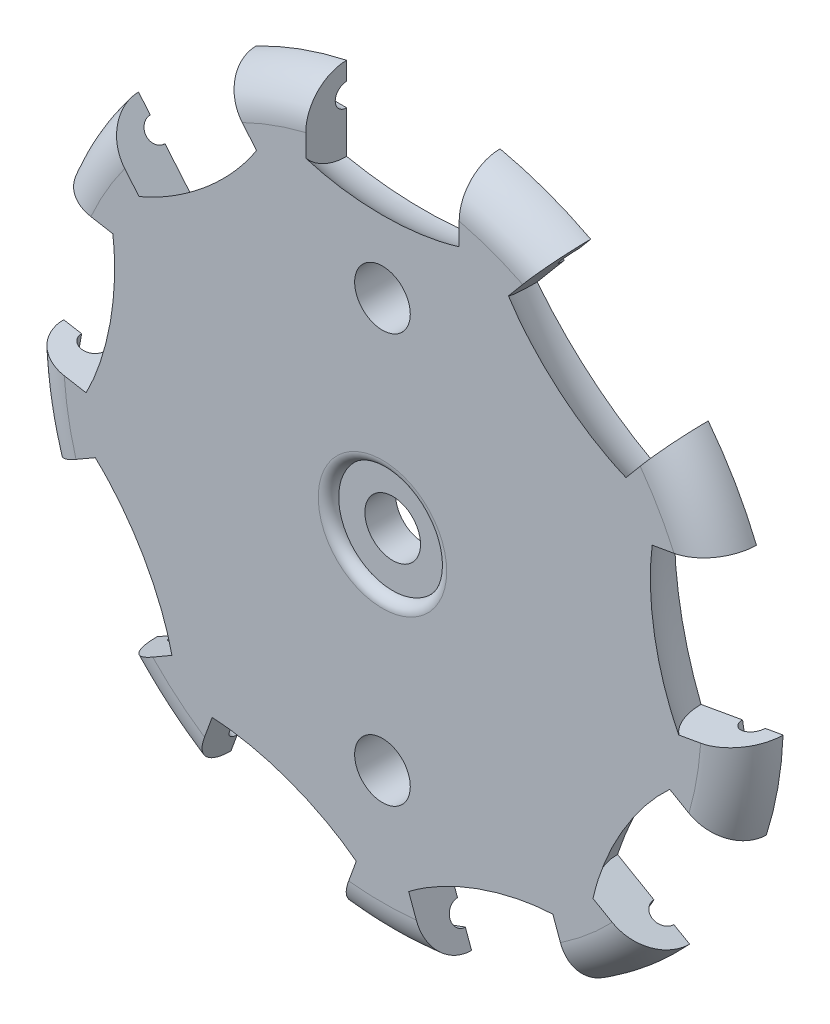
SolidWorks part; units mm, degrees
ref_plane "Front Plane" through (0, 0, 0) normal (0, 0, 1) x (1, 0, 0)
ref_plane "Top Plane" through (0, 0, 0) normal (0, 1, 0) x (1, 0, 0)
ref_plane "Right Plane" through (0, 0, 0) normal (1, 0, 0) x (0, 0, -1)
sketch "Sketch1" plane through (0, 0, 0) normal (0, 0, 1) x (1, 0, 0)
  circle A0 centre (0, 0) radius 27.94
  dimension "D1" = 55.88
extrude "Boss-Extrude1" add sketch "Sketch1" along normal blind 3.175
fillet "Fillet1" radius 3.1852 1 edges at (27.94, 0, 3.175)
sketch "Sketch2" plane through (0, 0, 3.175) normal (0, 0, 1) x (1, 0, 0)
  line L0 (0, -15.875) -> (0, 15.875) construction
  line L1 (0, 0) -> (0, 6.4682) construction
  circle A0 centre (0, 15.875) radius 2.159
  circle A1 centre (0, -15.875) radius 2.159
  circle A4 centre (0, 0) radius 2.159
  point P9 (0, 0)
  dimension "D2" = 4.318
  dimension "D4" = 4.318
  dimension "D1" = 15.875
  dimension "D3" = 2
extrude "Cut-Extrude1" cut sketch "Sketch2" against normal through all
sketch "Sketch5" plane through (0, 0, 0) normal (0, 0, 1) x (1, 0, 0)
  line L0 (-5.9531, 24.9936) -> (5.9531, 24.9936)
  line L1 (5.9531, 24.9936) -> (5.9531, 29.1545)
  line L2 (-5.9531, 24.9936) -> (-5.9531, 29.1545)
  line L3 (-5.9531, 24.9936) -> (-8.5086, 24.9936) construction
  arc A0 (-5.9531, 29.1545) -> (5.9531, 29.1545) centre (0, 0) cw
  circle A1 centre (0, 0) radius 27.94 construction
  point P5 (0, 24.9936)
  point P9 (0, 29.7561)
  dimension "D1" = 11.9062
  dimension "D2" = 24.9936
  dimension "D3" = 9.525
revolve "Cut-Revolve1" cut sketch "Sketch5" angle 360 about L3
sketch "Sketch6" plane through (0, 0, 0) normal (1, 0, 0) x (0, 0, -1)
  line L0 (0, -27.94) -> (0, 27.2984) construction
  circle A0 centre (0, 24.9936) radius 0.889
  arc A1 (-3.175, 22.3043) -> (0, 20.8327) centre (0, 24.9936) ccw construction
  dimension "D1" = 1.778
extrude "Cut-Extrude2" cut sketch "Sketch6" against normal mid plane 15.875
pattern_circular "CirPattern1" count 9 over 360 about axis through (0, 0, 0) along (0, 0, 1) of "Cut-Revolve1", "Cut-Extrude2"
sketch "Sketch8" plane through (0, 0, 3.175) normal (0, 0, 1) x (1, 0, 0)
  line L1 (0, 5.1326) -> (-4.445, 2.5663)
  line L2 (-4.445, 2.5663) -> (-4.445, -2.5663)
  line L3 (-4.445, -2.5663) -> (0, -5.1326)
  line L4 (0, -5.1326) -> (4.445, -2.5663)
  line L5 (4.445, -2.5663) -> (4.445, 2.5663)
  line L6 (4.445, 2.5663) -> (0, 5.1326)
  circle A0 centre (0, 0) radius 4.445 construction
  dimension "D1" = 8.89
extrude "Cut-Extrude4" [suppressed] cut sketch "Sketch8" against normal blind 1.5875
sketch "Sketch9" plane through (0, 0, 3.175) normal (0, 0, 1) x (1, 0, 0)
  circle A0 centre (0, 0) radius 4.191
  dimension "D1" = 8.382
extrude "Cut-Extrude5" cut sketch "Sketch9" against normal blind 0.7937
fillet "Fillet2" radius 0.7937 1 edges at (4.191, 0, 3.175)
